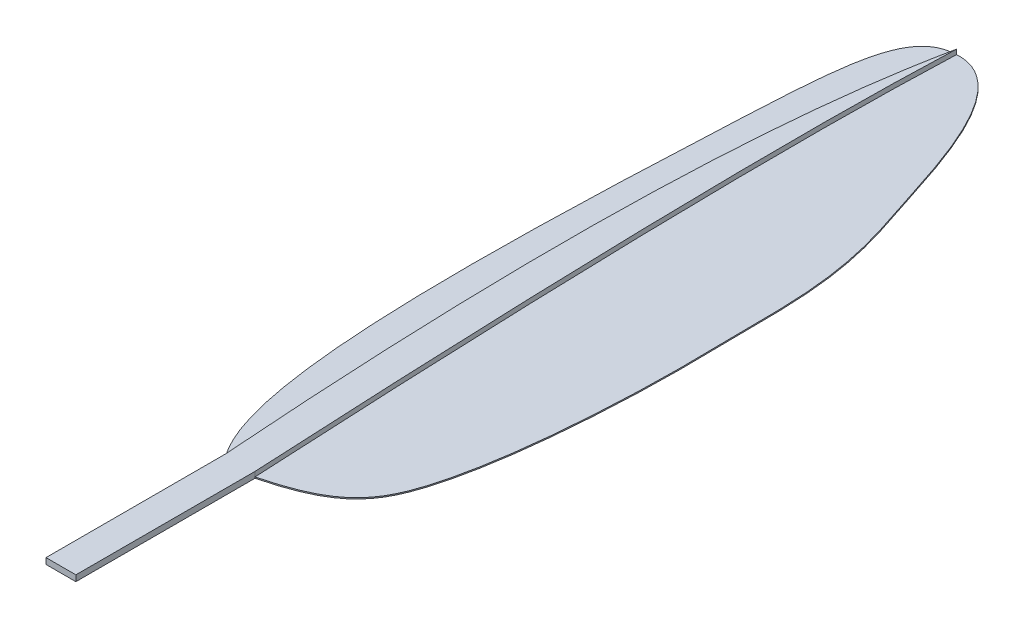
SolidWorks part; units mm, degrees
ref_plane "Front Plane" through (0, 0, 0) normal (0, 0, 1) x (1, 0, 0)
ref_plane "Top Plane" through (0, 0, 0) normal (0, 1, 0) x (1, 0, 0)
ref_plane "Right Plane" through (0, 0, 0) normal (1, 0, 0) x (0, 0, -1)
sketch "Sketch2" plane through (0, 0, 0) normal (0, 1, 0) x (1, 0, 0)
  line L0 (0, 0) -> (0, 120) construction
  line L1 (0, 0) -> (0, -30) construction
  line L3 (-2.5, 0) -> (2.5, 0) construction
  line L4 (-2.5, 0) -> (-2.5, -30)
  line L5 (-2.5, -30) -> (2.5, -30)
  line L6 (2.5, 0) -> (2.5, -30)
  spline S0 degree 3 poles (2.5, 0) (12.9304, 2.6479) (20.6328, 11.6617) (22.5218, 44.6896) (22.0541, 66.9531) (22.561, 78.1479) (15.3522, 99.0843) (8.9424, 120.5671) (0, 120) knots 0 0 0 0 0.1561 0.394681 0.460941 0.752435 0.809985 1 1 1 1
  spline S1 degree 2 poles (2.5, 0) (-1.6392, 79.8302) (0, 120) knots 0 0 0 1 1 1
  spline S2 degree 2 poles (-2.5, 0) (-8.3315, 79.8852) (0, 120) knots 0 0 0 1 1 1
  spline S3 degree 3 poles (0, 120) (-7.3575, 119.7562) (-8.1695, 106.9325) (-11.3784, 37.6138) (-9.5577, 8.3833) (-2.5, 0) knots 0 0 0 0 0.317116 0.417116 1 1 1 1
  point P10 (10.0606, 113.4257)
  point P12 (18.1675, 54.0195)
  point P14 (14.1805, 111.4322)
  point P15 (21.8887, 54.2853)
  point P16 (18.6991, 104.6543)
  point P17 (-9.2099, 84.3207)
  point P18 (17.0242, 102.9111)
  point P19 (13.9343, 105.0043)
  point P20 (15.8281, 105.0043)
  point P21 (17.2236, 95.9339)
  point P22 (17.9213, 91.6478)
  point P23 (22.307, 54.3694)
  dimension "D1" = 5
  dimension "40" = 30
  dimension "160" = 120
extrude "Boss-Extrude1" add sketch "Sketch2" along normal blind 1 contours S2 L4 L5 L6 S1 region at (-1.3307, 0, -34.7224)
extrude "Boss-Extrude2" add sketch "Sketch2<4>" along normal blind 0.2 contours S1 S0 | S2 S3 region at (-6.3643, 0, -62.6603) region at (9.9715, 0, -58.4417)
sketch "Sketch2<4>" plane through (0, 0, 0) normal (0, 1, 0) x (1, 0, 0) same geometry as "Sketch2"
